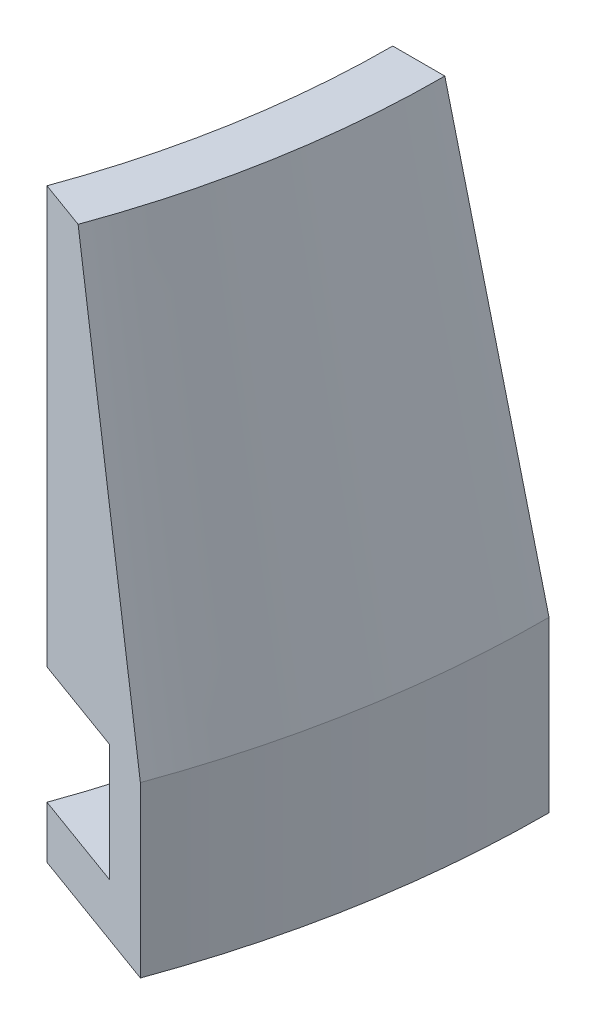
SolidWorks part; units mm, degrees
material "ABS"
ref_plane "Front Plane" through (0, 0, 0) normal (0, 0, 1) x (1, 0, 0)
ref_plane "Top Plane" through (0, 0, 0) normal (0, 1, 0) x (1, 0, 0)
ref_plane "Right Plane" through (0, 0, 0) normal (1, 0, 0) x (0, 0, -1)
sketch "Sketch1" plane through (0, 0, 0) normal (0, 0, 1) x (1, 0, 0)
  line L0 (0, 0) -> (0, 50.8)
  line L1 (0, 0) -> (12.7, 0)
  line L2 (12.7, 0) -> (12.7, -14.2875)
  line L3 (12.7, -14.2875) -> (0, -14.2875)
  line L4 (0, -14.2875) -> (0, -20.6375)
  line L5 (0, -20.6375) -> (19.05, -20.6375)
  line L6 (19.05, -20.6375) -> (19.05, 0)
  line L7 (19.05, 0) -> (6.35, 50.8)
  line L8 (6.35, 50.8) -> (0, 50.8)
  dimension "D1" = 50.8
  dimension "D2" = 12.7
  dimension "D3" = 14.2875
  dimension "D4" = 6.35
  dimension "D5" = 19.05
  dimension "D6" = 6.35
  dimension "D7" = 50.8
sketch "Sketch2" plane through (0, 0, 0) normal (0, 0, 1) x (1, 0, 0)
  line L0 (-104.775, 37.3055) -> (-104.775, 0)
  line L1 (12.7, 0) -> (12.7, -14.2875) construction
  dimension "D1" = 117.475
ref_axis "Axis1" through (-104.775, 37.3055, 0) along (0, -1, 0)
revolve "Revolve1" add sketch "Sketch1" angle 20 about L0 region at (8.2052, 12.7156, 0)
